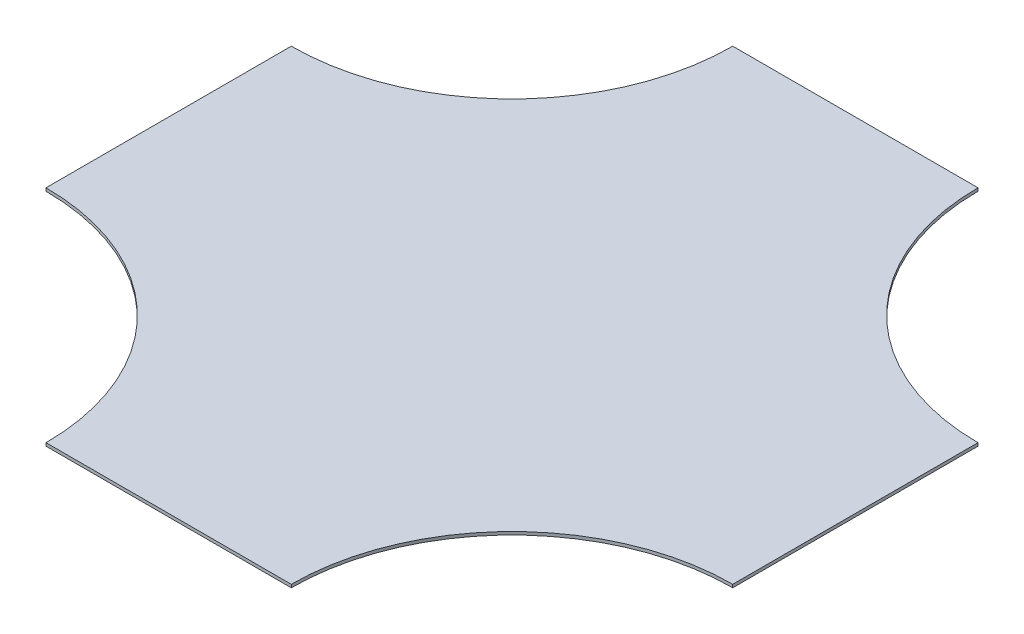
SolidWorks part; units mm, degrees
material "6061 Alloy"
ref_plane "Front Plane" through (0, 0, 0) normal (0, 0, 1) x (1, 0, 0)
ref_plane "Top Plane" through (0, 0, 0) normal (0, 1, 0) x (1, 0, 0)
ref_plane "Right Plane" through (0, 0, 0) normal (1, 0, 0) x (0, 0, -1)
sketch "Sketch1" plane through (0, 0, 0) normal (0, 1, 0) x (1, 0, 0)
  line L9 (-127, -355.6) -> (127, -355.6)
  line L10 (-355.6, -127) -> (-355.6, 127)
  line L11 (-127, 355.6) -> (127, 355.6)
  line L12 (355.6, -127) -> (355.6, 127)
  line L13 (-193.9554, -193.9554) -> (193.9554, 193.9554) construction
  line L14 (-193.9554, 193.9554) -> (193.9554, -193.9554) construction
  arc A8 (-355.6, 127) -> (-127, 355.6) centre (-355.6, 355.6) ccw
  arc A9 (127, 355.6) -> (355.6, 127) centre (355.6, 355.6) ccw
  arc A10 (355.6, -127) -> (127, -355.6) centre (355.6, -355.6) ccw
  arc A11 (-127, -355.6) -> (-355.6, -127) centre (-355.6, -355.6) ccw
  point P0 (0, 0)
  point P1 (0, 0)
  point P2 (0, 0)
  dimension "D3" = 457.2
  dimension "D4" = 457.2
  dimension "D5" = 457.2
  dimension "D6" = 457.2
  dimension "D1" = 711.2
  dimension "D2" = 711.2
extrude "Boss-Extrude1" add sketch "Sketch1" along normal blind 3.175
